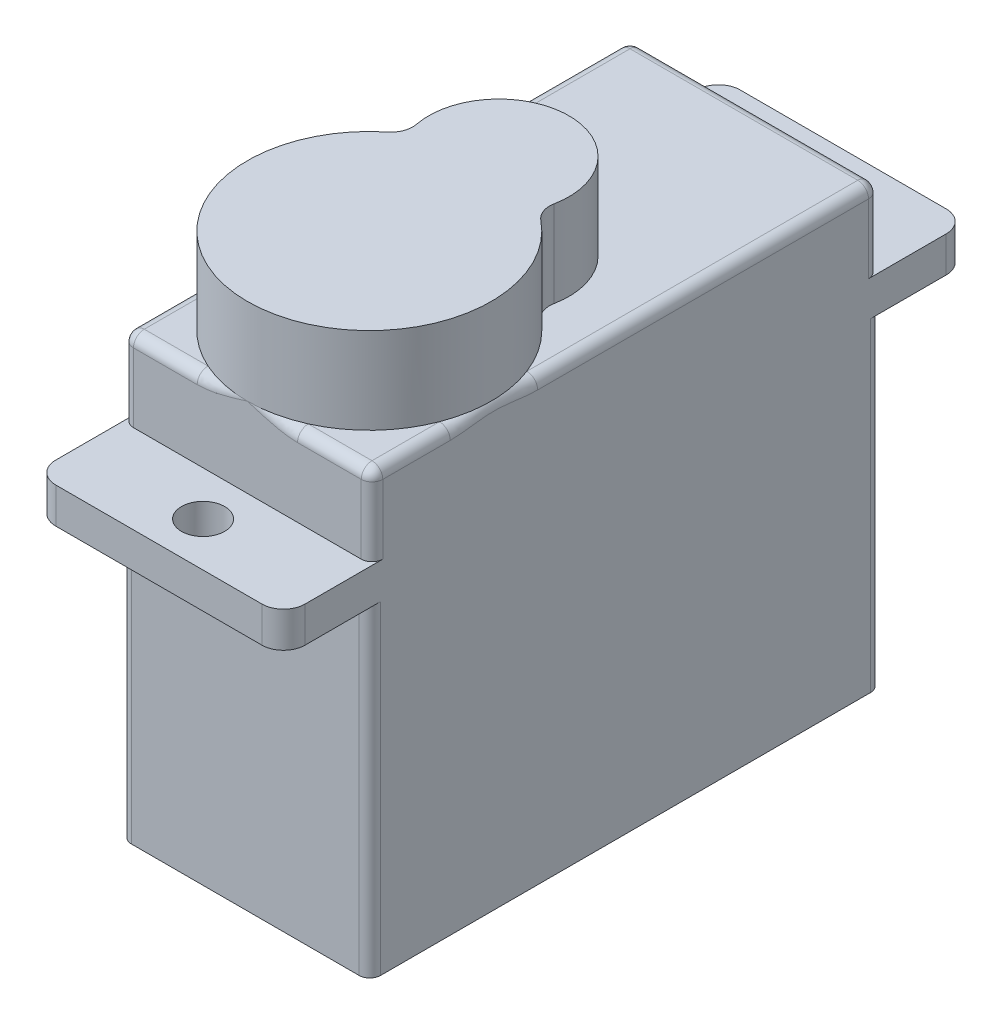
SolidWorks part; units mm, degrees
ref_plane "Front Plane" through (0, 0, 0) normal (0, 0, 1) x (1, 0, 0)
ref_plane "Top Plane" through (0, 0, 0) normal (0, 1, 0) x (1, 0, 0)
ref_plane "Right Plane" through (0, 0, 0) normal (1, 0, 0) x (0, 0, -1)
sketch "Sketch1" plane through (0, 0, 0) normal (0, 1, 0) x (1, 0, 0)
  line L1 (-5.775, -11.85) -> (5.775, -11.85)
  line L2 (-5.775, -11.85) -> (-5.775, 11.85)
  line L3 (-5.775, 11.85) -> (5.775, 11.85)
  line L4 (5.775, -11.85) -> (5.775, 11.85)
  line L5 (-5.775, -11.85) -> (5.775, 11.85) construction
  line L6 (-5.775, 11.85) -> (5.775, -11.85) construction
  point P0 (0, 0)
  dimension "D1" = 23.7
  dimension "D2" = 11.55
extrude "Boss-Extrude1" add sketch "Sketch1" along normal blind 15
sketch "Sketch2" plane through (0, 15, 0) normal (0, 1, 0) x (1, 0, 0)
  line L0 (5.775, 11.85) -> (-5.775, 11.85) construction
  line L1 (-5.775, -15.85) -> (5.775, -15.85)
  line L2 (-5.775, -15.85) -> (-5.775, 15.85)
  line L3 (-5.775, 15.85) -> (5.775, 15.85)
  line L4 (5.775, -15.85) -> (5.775, 15.85)
  line L5 (-5.775, -15.85) -> (5.775, 15.85) construction
  line L6 (-5.775, 15.85) -> (5.775, -15.85) construction
  line L7 (5.775, -11.85) -> (5.775, 11.85) construction
  point P0 (0, 0)
  dimension "D1" = 4
  dimension "D2" = 0
extrude "Boss-Extrude2" add sketch "Sketch2" along normal blind 1.65
fillet "Fillet1" radius 1 4 edges at (-5.775, 15.825, -15.85) (5.775, 15.825, -15.85) (5.775, 15.825, 15.85) (-5.775, 15.825, 15.85)
sketch "Sketch3" plane through (0, 16.65, 0) normal (0, 1, 0) x (1, 0, 0)
  line L0 (5.775, -14.85) -> (5.775, 14.85) construction
  line L1 (-5.775, -11.75) -> (5.775, -11.75)
  line L2 (-5.775, -11.75) -> (-5.775, 11.75)
  line L3 (-5.775, 11.75) -> (5.775, 11.75)
  line L4 (5.775, -11.75) -> (5.775, 11.75)
  line L5 (-5.775, -11.75) -> (5.775, 11.75) construction
  line L6 (-5.775, 11.75) -> (5.775, -11.75) construction
  point P0 (0, 0)
  dimension "D1" = 23.5
extrude "Boss-Extrude3" add sketch "Sketch3" along normal blind 3.7
sketch "Sketch4" plane through (0, 16.65, 0) normal (0, 1, 0) x (1, 0, 0)
  line L0 (0, 15.85) -> (0, 11.75) construction
  line L1 (4.775, 15.85) -> (-4.775, 15.85) construction
  line L2 (5.775, 11.75) -> (-5.775, 11.75) construction
  line L3 (0, -15.85) -> (0, -11.75) construction
  line L4 (-4.775, -15.85) -> (4.775, -15.85) construction
  line L5 (-5.775, -11.75) -> (5.775, -11.75) construction
  circle A0 centre (0, 13.8) radius 1
  circle A1 centre (0, -13.8) radius 1
  dimension "D1" = 2
  dimension "D2" = 2
extrude "Cut-Extrude1" cut sketch "Sketch4" against normal blind 3.7
sketch "Sketch5" plane through (0, 20.35, 0) normal (0, 1, 0) x (1, 0, 0)
  line L0 (-5.775, -11.75) -> (5.775, -11.75) construction
  circle A0 centre (0, -6.1) radius 5.65
  dimension "D1" = 11.3
  dimension "D2" = 5.65
extrude "Boss-Extrude4" add sketch "Sketch5" along normal blind 4
fillet "Fillet3" [suppressed] radius 1
fillet "Fillet2" radius 0.5 13 edges at (-5.775, 7.5, -11.85) (-5.775, 18.5, -11.75) (5.775, 18.5, -11.75) (5.775, 7.5, -11.85) (-5.775, 18.5, 11.75) (5.775, 18.5, 11.75) (-5.775, 7.5, 11.85) (5.775, 7.5, 11.85) (0, 20.35, -11.75) (5.775, 20.35, 0) (-5.775, 20.35, 0) (-2.8875, 20.35, 11.75) (2.8875, 20.35, 11.75)
ref_axis "Axis1" through (0, 42.8939, 6.1) along (0, -1, 0)
sketch "Sketch6" plane through (0, 20.35, 0) normal (0, 1, 0) x (1, 0, 0)
  circle A0 centre (0, -0.1) radius 3.25
  dimension "D1" = 6
  dimension "D2" = 6.5
extrude "Boss-Extrude5" add sketch "Sketch6" along normal blind 4
fillet "Fillet4" radius 1 2 edges at (3.0123, 22.35, 1.32) (-3.0123, 22.35, 1.32)
